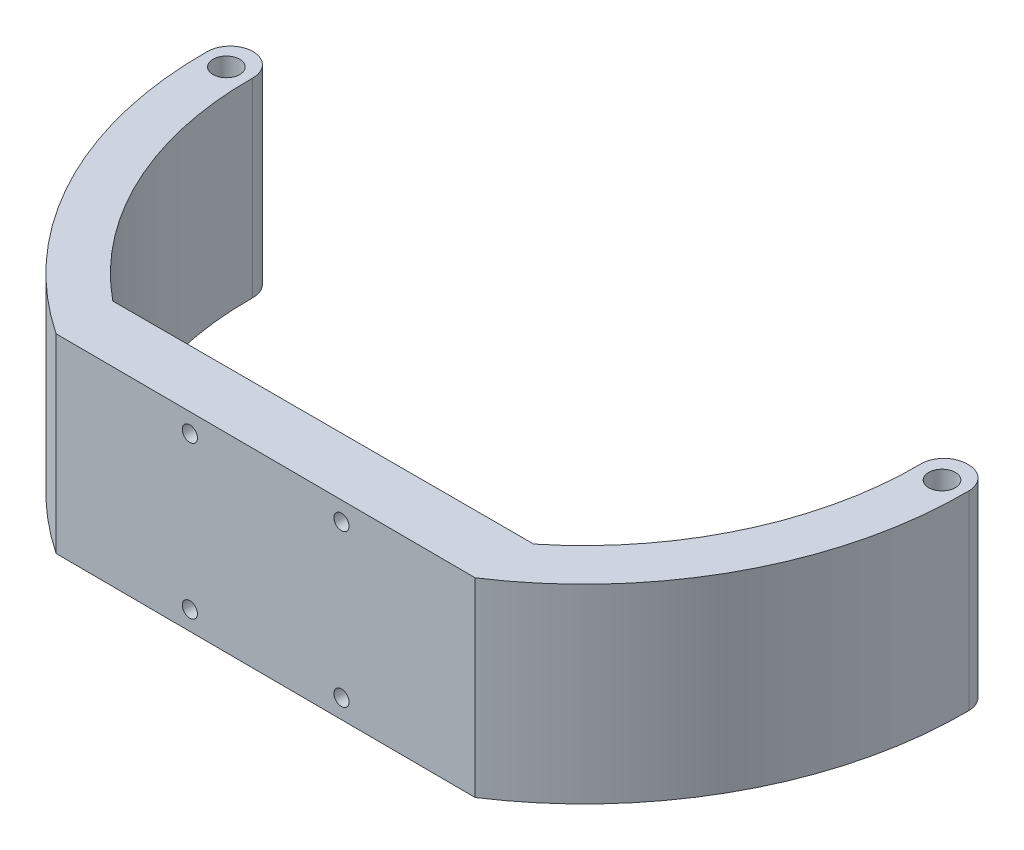
SolidWorks part; units mm, degrees
ref_plane "Front Plane" through (0, 0, 0) normal (0, 0, 1) x (1, 0, 0)
ref_plane "Top Plane" through (0, 0, 0) normal (0, 1, 0) x (1, 0, 0)
ref_plane "Right Plane" through (0, 0, 0) normal (1, 0, 0) x (0, 0, -1)
sketch "Sketch1" plane through (0, 0, 0) normal (0, 1, 0) x (1, 0, 0)
  line L0 (49.8593, 3.7482) -> (43.6644, 3.2233)
  line L2 (-49.8593, 3.7482) -> (-43.8892, 3.2423)
  line L4 (-27.8217, -34.0987) -> (27.4635, -34.0987)
  line L5 (-27.8217, -41.5446) -> (27.4635, -41.7822)
  circle A2 centre (-47, 0) radius 1.75
  arc A4 (-27.8217, -34.0987) -> (-43.8892, 3.2423) centre (0, 0) cw
  arc A12 (27.4635, -34.0987) -> (43.6644, 3.2233) centre (0, 0) ccw
  circle A13 centre (47, 0) radius 1.75
  arc A14 (-27.8217, -41.5446) -> (-49.8593, 3.7482) centre (0, 0) cw
  arc A15 (27.4635, -41.7822) -> (49.8593, 3.7482) centre (0, 0) ccw
  point P7 (0, 0)
extrude "Boss-Extrude1" add sketch "Sketch1" along normal blind 25
fillet "Fillet2" radius 3 3 edges at (43.6644, 12.5, -3.2233) (-43.8892, 12.5, -3.2423) (49.8593, 12.5, -3.7482)
fillet "Fillet3" radius 3 1 edges at (-49.8593, 12.5, -3.7482)
sketch "Sketch2" plane through (-0.1791, 0, 41.6634) normal (-0.0043, 0, 1) x (1, 0, 0.0043)
  line L8 (10, 2.5) -> (-10, 22.5) construction
  line L9 (10, 22.5) -> (-10, 2.5) construction
  circle A0 centre (10, 2.5) radius 1
  circle A1 centre (-10, 2.5) radius 1
  circle A2 centre (10, 22.5) radius 1
  circle A3 centre (-10, 22.5) radius 1
  point P6 (0, 12.5)
extrude "Cut-Extrude1" cut sketch "Sketch2" against normal blind 10
